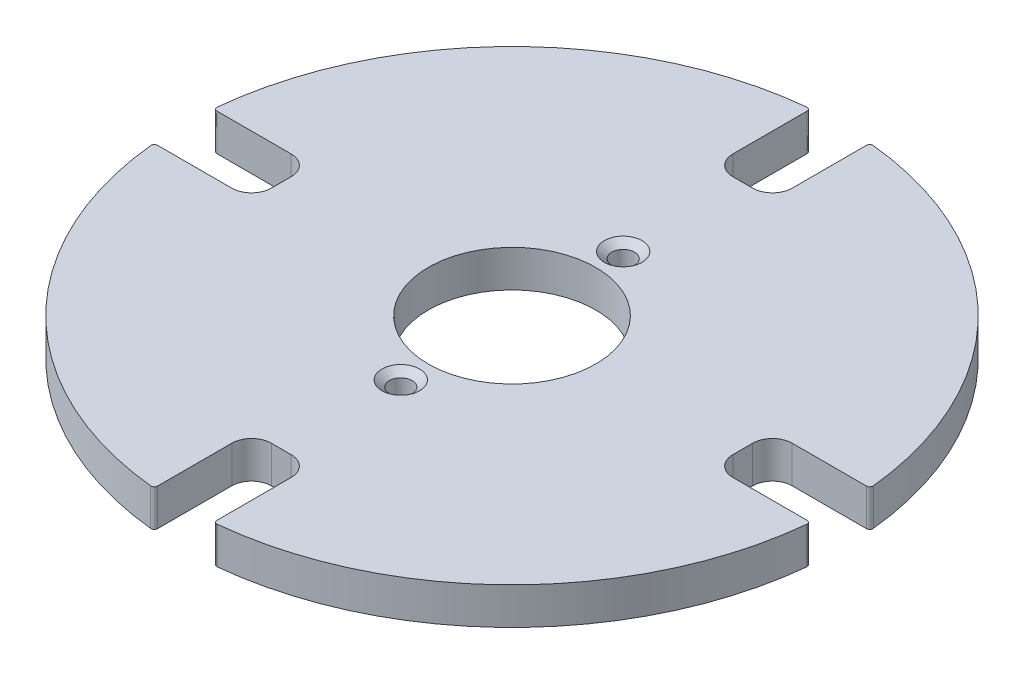
SolidWorks part; units mm, degrees
ref_plane "Front Plane" through (0, 0, 0) normal (0, 0, 1) x (1, 0, 0)
ref_plane "Top Plane" through (0, 0, 0) normal (0, 1, 0) x (1, 0, 0)
ref_plane "Right Plane" through (0, 0, 0) normal (1, 0, 0) x (0, 0, -1)
sketch "Sketch3" plane through (0, 0, 0) normal (0, 1, 0) x (1, 0, 0)
  circle A0 centre (0, 0) radius 50
  circle A1 centre (0, 0) radius 12.7
  circle A2 centre (0, 0) radius 16.8627 construction
  dimension "D1" = 25.4
extrude "Boss-Extrude4" add sketch "Sketch3" along normal blind 5.6
sketch "Sketch6" plane through (0, 0, 0) normal (0, 1, 0) x (1, 0, 0)
  line L0 (0, 0) -> (89.4122, 0) construction
  line L1 (-38, -4.5) -> (-65, -4.5)
  line L2 (-35, -1.5) -> (-35, 1.5)
  line L3 (-38, 4.5) -> (-65, 4.5)
  line L4 (-65, -4.5) -> (-65, 4.5)
  line L5 (-35, -4.5) -> (-65, 4.5) construction
  line L6 (-35, 4.5) -> (-65, -4.5) construction
  line L7 (0, 0) -> (0, -68.3888) construction
  line L8 (0, 0) -> (0, 80.8497) construction
  line L9 (-4.5, 38) -> (-4.5, 65)
  line L10 (-1.5, 35) -> (1.5, 35)
  line L11 (4.5, 38) -> (4.5, 65)
  line L12 (-4.5, 65) -> (4.5, 65)
  line L13 (-4.5, 35) -> (4.5, 65) construction
  line L14 (4.5, 35) -> (-4.5, 65) construction
  line L15 (38, 4.5) -> (65, 4.5)
  line L16 (35, 1.5) -> (35, -1.5)
  line L17 (38, -4.5) -> (65, -4.5)
  line L18 (65, 4.5) -> (65, -4.5)
  line L19 (35, 4.5) -> (65, -4.5) construction
  line L20 (35, -4.5) -> (65, 4.5) construction
  line L21 (4.5, -38) -> (4.5, -65)
  line L22 (1.5, -35) -> (-1.5, -35)
  line L23 (-4.5, -38) -> (-4.5, -65)
  line L24 (0, 0) -> (-101.315, 0) construction
  line L25 (4.5, -65) -> (-4.5, -65)
  line L26 (4.5, -35) -> (-4.5, -65) construction
  line L27 (-4.5, -35) -> (4.5, -65) construction
  circle A0 centre (0, 0) radius 50 construction
  arc A1 (-38, 4.5) -> (-35, 1.5) centre (-38, 1.5) cw
  arc A2 (-38, -4.5) -> (-35, -1.5) centre (-38, -1.5) ccw
  arc A3 (4.5, 38) -> (1.5, 35) centre (1.5, 38) cw
  arc A4 (-4.5, 38) -> (-1.5, 35) centre (-1.5, 38) ccw
  arc A5 (38, -4.5) -> (35, -1.5) centre (38, -1.5) cw
  arc A6 (38, 4.5) -> (35, 1.5) centre (38, 1.5) ccw
  arc A7 (-4.5, -38) -> (-1.5, -35) centre (-1.5, -38) cw
  arc A8 (4.5, -38) -> (1.5, -35) centre (1.5, -38) ccw
  point P0 (-50, 0)
  point P21 (0, 50)
  point P22 (0, 0)
  point P33 (50, 0)
  point P41 (0, 5.6)
  point P42 (0, 0)
  point P46 (0, -50)
  point P47 (2.6408, 2.6408)
  point P51 (-2.6408, -2.6408)
  point P54 (0, 0.5)
  point P61 (0, 0)
  dimension "D3" = 3
  dimension "D4" = 3
  dimension "D1" = 9
  dimension "D2" = 30
  dimension "D5" = 4
extrude "Cut-Extrude18" cut sketch "Sketch6" along normal blind 10
sketch "Sketch7" plane through (0, 0, 0) normal (0, 1, 0) x (1, 0, 0)
  line L0 (0, 0) -> (92.619, 0) construction
  line L1 (0, 0) -> (-95.6074, 0) construction
  line L2 (0, 0) -> (0, -61.0615) construction
  line L3 (0, 0) -> (0, 63.4251) construction
  circle A4 centre (0, 0) radius 50
  dimension "D1" = 100
fillet "Fillet2" radius 0.5 8 edges at (-49.7971, 2.8, 4.5) (-49.7971, 2.8, -4.5) (4.5, 2.8, -49.7971) (-4.5, 2.8, -49.7971) (49.7971, 2.8, -4.5) (49.7971, 2.8, 4.5) (4.5, 2.8, 49.7971) (-4.5, 2.8, 49.7971)
hole_wizard "CSK for #4 Flat Head Machine Screw (100)1" positions "Sketch9" profile "Sketch8" countersink size "#4" standard "ANSI Inch" end condition through all
sketch "Sketch9" plane through (0, 5.6, 0) normal (0, 1, 0) x (1, 0, 0)
  line L0 (0, 0) -> (0, -61.0615) construction
  circle A0 centre (0, 0) radius 16.8627 construction
  point P0 (0, -16.8627)
  point P6 (0, 16.8627)
sketch "Sketch8" plane through (0, 5.6, 16.8627) normal (1, 0, 0) x (0, 0, 1)
  line L0 (0, 0) -> (0, 5.6)
  line L1 (0, 5.6) -> (1.7272, 5.6)
  line L2 (1.7272, 5.6) -> (1.7272, 0.9484)
  line L3 (1.7272, 0.9484) -> (2.8575, 0)
  line L5 (2.8575, 0) -> (0, 0)
  line L6 (-1.7272, 0.9484) -> (-2.8575, 0) construction
  line L11 (0, -6.35) -> (0, 107.95) construction
  dimension "Thru Hole Dia." = 3.4544
  dimension "Thru Hole Depth" = 5.6
  dimension "Near C'Sink Dia." = 5.715
  dimension "Near C'Sink Angle" = 100
